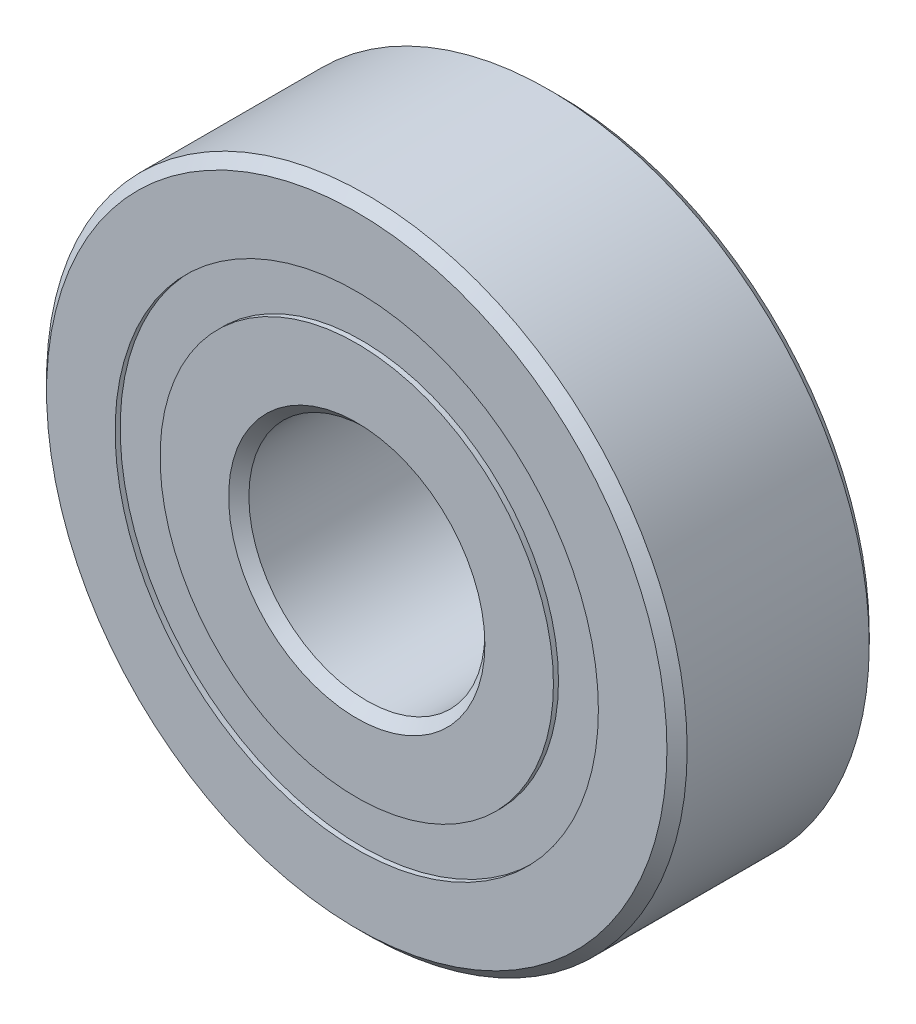
SolidWorks part; units mm, degrees
ref_plane "Front Plane" through (0, 0, 0) normal (0, 0, 1) x (1, 0, 0)
ref_plane "Top Plane" through (0, 0, 0) normal (0, 1, 0) x (1, 0, 0)
ref_plane "Right Plane" through (0, 0, 0) normal (1, 0, 0) x (0, 0, -1)
sketch "Sketch1" plane through (0, 0, 0) normal (1, 0, 0) x (0, 0, -1)
  line L0 (-3, 0) -> (3, 0) construction
  line L1 (0, 9.5) -> (0, -9.5) construction
  line L2 (2.7, 9.5) -> (-2.7, 9.5)
  line L3 (-2.7, 9.5) -> (-3, 9.2)
  line L4 (-3, 9.2) -> (-3, 7.1667)
  line L5 (-3, 7.1667) -> (-1.3333, 7.1667)
  line L6 (3, 7.1667) -> (1.3333, 7.1667)
  line L7 (3, 9.2) -> (3, 7.1667)
  line L8 (2.7, 9.5) -> (3, 9.2)
  line L9 (0, 9.5) -> (0, 6.5) construction
  line L10 (0, 6.5) -> (0, 3.5) construction
  arc A0 (-1.3333, 7.1667) -> (1.3333, 7.1667) centre (0, 6.5) cw
  arc A1 (-1.3333, 7.1667) -> (1.3333, 7.1667) centre (0, 6.5) ccw construction
  point P14 (0, 3.5)
  point P15 (0, -3.5)
  dimension "Width" = 6
  dimension "OD" = 19
  dimension "D1" = 45
  dimension "D2" = 0.3
  dimension "D3" = 2.6667
  dimension "Shaft Dia" = 7
  dimension "D4" = 0.6667
revolve "Revolve1" add sketch "Sketch1" angle 360 about L0
sketch "Sketch2" plane through (0, 0, 0) normal (1, 0, 0) x (0, 0, -1)
  line L0 (-3, 5.8333) -> (-1.3333, 5.8333)
  line L1 (-3, 9.2) -> (-3, -9.2) construction
  line L2 (-3, 5.8333) -> (-3, 3.8)
  line L3 (-3, 3.8) -> (-2.7, 3.5)
  line L4 (-2.7, 3.5) -> (2.7, 3.5)
  line L5 (0, 9.5) -> (0, -9.5) construction
  line L6 (0, 3.5) -> (0, 5.0093) construction
  line L7 (0, 5.0093) -> (0, 3.5) construction
  line L8 (-3, 5.8333) -> (-3, 1.7667) construction
  line L10 (3, 5.8333) -> (1.3333, 5.8333)
  line L11 (3, 5.8333) -> (3, 3.8)
  line L12 (3, 3.8) -> (2.7, 3.5)
  arc A0 (-1.3333, 5.8333) -> (1.3333, 5.8333) centre (0, 6.5) ccw
  arc A1 (1.3333, 7.1667) -> (-1.3333, 7.1667) centre (0, 6.5) ccw construction
  circle A2 centre (0, 6.5) radius 1.4907 construction
  dimension "D1" = 0.3
  dimension "D2" = 45
revolve "Revolve2" add sketch "Sketch2" angle 360 about L0
sketch "Sketch3" plane through (0, 0, 0) normal (1, 0, 0) x (0, 0, -1)
  line L0 (-1.4907, 6.5) -> (1.4907, 6.5)
  line L1 (0, 6.5) -> (0, 0) construction
  circle A1 centre (0, 6.5) radius 1.4907 construction
  arc A2 (-1.4907, 6.5) -> (1.4907, 6.5) centre (0, 6.5) cw
  arc A3 (1.3333, 7.1667) -> (-1.3333, 7.1667) centre (0, 6.5) ccw construction
  dimension "D1" = 2.9814
  dimension "D2" = 6.5
revolve "Revolve3" add sketch "Sketch3" angle 360 about L0
ref_axis "Axis1" through (0, 0, -3) along (0, 0, 1)
pattern_circular "CirPattern1" count 13 every 27.692 about axis through (0, 0, -3) along (0, 0, 1) of bodies 104
sketch "Sketch5" plane through (0, 0, 0) normal (1, 0, 0) x (0, 0, -1)
  line L0 (-3, 5.8333) -> (-1.3333, 5.8333) construction
  line L1 (-2.85, 7.1667) -> (-1.4907, 7.1667)
  line L2 (-2.85, 7.1667) -> (-2.85, 5.8333)
  line L3 (-2.85, 5.8333) -> (-1.4907, 5.8333)
  line L4 (-1.4907, 7.1667) -> (-1.4907, 5.8333)
  line L5 (1.4907, 7.1667) -> (2.85, 7.1667)
  line L6 (1.4907, 7.1667) -> (1.4907, 5.8333)
  line L7 (1.4907, 5.8333) -> (2.85, 5.8333)
  line L8 (2.85, 7.1667) -> (2.85, 5.8333)
  line L9 (-3, 7.1667) -> (-1.3333, 7.1667) construction
  line L10 (-2.85, 9.35) -> (-2.85, 7.1667) construction
  line L11 (-2.7, 9.5) -> (-3, 9.2) construction
  circle A0 centre (0, 6.5) radius 1.4907 construction
revolve "Revolve5" add sketch "Sketch5" angle 360 about L0
sketch "Sketch6" plane through (0, 0, 0) normal (0, 1, 0) x (1, 0, 0)
  point P0 (9.5, -3)
  point P1 (9.5, 3)
  dimension "D1" = 6
ref_axis "Center Axis 1" through (0, 0, -4.5516) along (0, 0, 1)
ref_plane "Contact Plane 1" through (0, 0, 3) normal (0, 0, 1) x (1, 0, 0)
ref_plane "Contact Plane 2" through (0, 0, -3) normal (0, 0, -1) x (-1, 0, 0)
equation "\"D2@Sketch1\" = \"Width@Sketch1\"*.05"
equation "\"D3@Sketch1\" = \"Width@Sketch1\"/2.25"
equation "\"D4@Sketch1\" = \"D3@Sketch1\"/4"
equation "\"Balls@CirPattern1\"=\"D2@Sketch3\"*2*pi/\"D1@Sketch3\"-1"
equation "\"D2@CirPattern1\" = 360/\"Balls@CirPattern1\""
equation "\"D1@Sketch2\"=\"D2@Sketch1\""
equation "\"D1@Sketch6\"=\"Width@Sketch1\""
